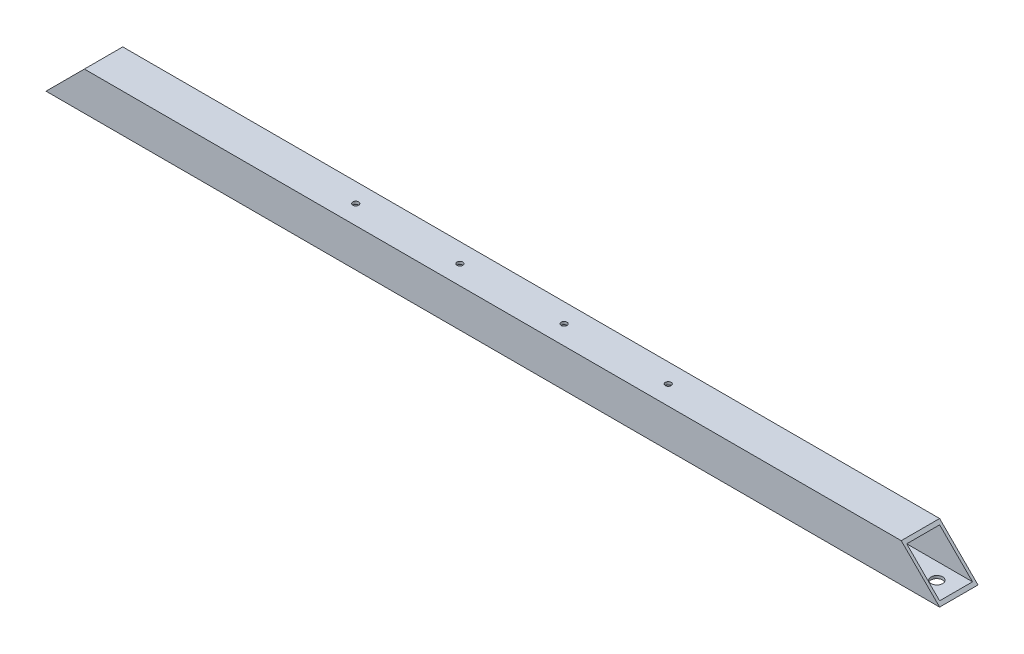
SolidWorks part; units mm, degrees
material "6061 Alloy"
ref_plane "Front Plane" through (0, 0, 0) normal (0, 0, 1) x (1, 0, 0)
ref_plane "Top Plane" through (0, 0, 0) normal (0, 1, 0) x (1, 0, 0)
ref_plane "Right Plane" through (0, 0, 0) normal (1, 0, 0) x (0, 0, -1)
sketch "Sketch1" plane through (0, 0, 0) normal (1, 0, 0) x (0, 0, -1)
  line L0 (19.05, -19.05) -> (19.05, 19.05)
  line L1 (-22.225, -22.225) -> (22.225, -22.225)
  line L2 (-22.225, -22.225) -> (-22.225, 22.225)
  line L3 (-22.225, 22.225) -> (22.225, 22.225)
  line L4 (22.225, -22.225) -> (22.225, 22.225)
  line L5 (-22.225, -22.225) -> (22.225, 22.225) construction
  line L6 (-22.225, 22.225) -> (22.225, -22.225) construction
  line L7 (-19.05, 19.05) -> (19.05, 19.05)
  line L8 (-19.05, -19.05) -> (-19.05, 19.05)
  line L9 (-19.05, -19.05) -> (19.05, -19.05)
  point P0 (0, 0)
  dimension "D1" = 44.45
  dimension "D2" = 3.175
extrude "Boss-Extrude1" add sketch "Sketch1" along normal blind 1035.05
sketch "Sketch2" plane through (0, 0, 22.225) normal (0, 0, 1) x (1, 0, 0)
  line L0 (517.525, 22.225) -> (517.525, -22.225) construction
  line L1 (1035.05, 22.225) -> (0, 22.225) construction
  line L2 (1035.05, -22.225) -> (0, -22.225) construction
  line L3 (0, 22.225) -> (0, -22.225)
  line L4 (0, -22.225) -> (44.45, 22.225)
  line L5 (44.45, 22.225) -> (0, 22.225)
  line L6 (990.6, 22.225) -> (1035.05, 22.225)
  line L7 (1035.05, -22.225) -> (990.6, 22.225)
  line L8 (1035.05, 22.225) -> (1035.05, -22.225)
extrude "Cut-Extrude1" cut sketch "Sketch2" against normal through all
hole_wizard "1/2 Clearance Hole1" positions "Sketch3" profile "Sketch4" hole size "1/2" standard "ANSI Inch" end condition through all
sketch "Sketch3" plane through (0, -22.225, 0) normal (0, -1, 0) x (-1, 0, 0)
  line L0 (-517.525, 22.225) -> (-517.525, -22.225) construction
  line L1 (-1035.05, 22.225) -> (0, 22.225) construction
  line L2 (-1035.05, -22.225) -> (0, -22.225) construction
  line L3 (0, 0) -> (-1035.05, 0) construction
  line L4 (-1035.05, -22.225) -> (-1035.05, 22.225) construction
  point P0 (-25.4, 0)
  point P10 (-1009.65, 0)
  point P17 (-52.6949, 0)
  dimension "D1" = 984.25
sketch "Sketch4" plane through (25.4, -22.225, 0) normal (1, 0, 0) x (0, 0, -1)
  line L0 (0, 0) -> (0, 44.45)
  line L1 (0, 44.45) -> (6.7462, 44.45)
  line L2 (6.7462, 44.45) -> (6.7462, 0)
  line L5 (6.7462, 0) -> (0, 0)
  line L11 (0, -6.35) -> (0, 107.95) construction
  dimension "Thru Hole Dia." = 13.4925
  dimension "Thru Hole Depth" = 44.45
hole_wizard "1/4 Clearance Hole1" positions "Sketch6" profile "Sketch7" hole size "1/4" standard "ANSI Inch" end condition through all
sketch "Sketch6" plane through (0, 22.225, 0) normal (0, 1, 0) x (1, 0, 0)
  line L0 (517.525, -22.225) -> (517.525, 22.225) construction
  line L1 (990.6, -22.225) -> (44.45, -22.225) construction
  line L2 (990.6, 22.225) -> (44.45, 22.225) construction
  line L3 (990.6, 0) -> (44.45, 0) construction
  line L4 (990.6, 22.225) -> (990.6, -22.225) construction
  line L5 (44.45, 22.225) -> (44.45, -22.225) construction
  point P0 (336.55, 0)
  point P2 (457.2, 0)
  point P12 (577.85, 0)
  point P13 (698.5, 0)
  point P21 (245.8989, -7.4171)
  point P22 (381.9782, 0)
  point P23 (224.2226, 0)
  dimension "D1" = 120.65
  dimension "D2" = 120.65
sketch "Sketch7" plane through (336.55, 22.225, 0) normal (1, 0, 0) x (0, 0, 1)
  line L0 (0, 0) -> (0, 44.45)
  line L1 (0, 44.45) -> (3.3782, 44.45)
  line L2 (3.3782, 44.45) -> (3.3782, 0)
  line L5 (3.3782, 0) -> (0, 0)
  line L11 (0, -6.35) -> (0, 107.95) construction
  dimension "Thru Hole Dia." = 6.7564
  dimension "Thru Hole Depth" = 44.45
